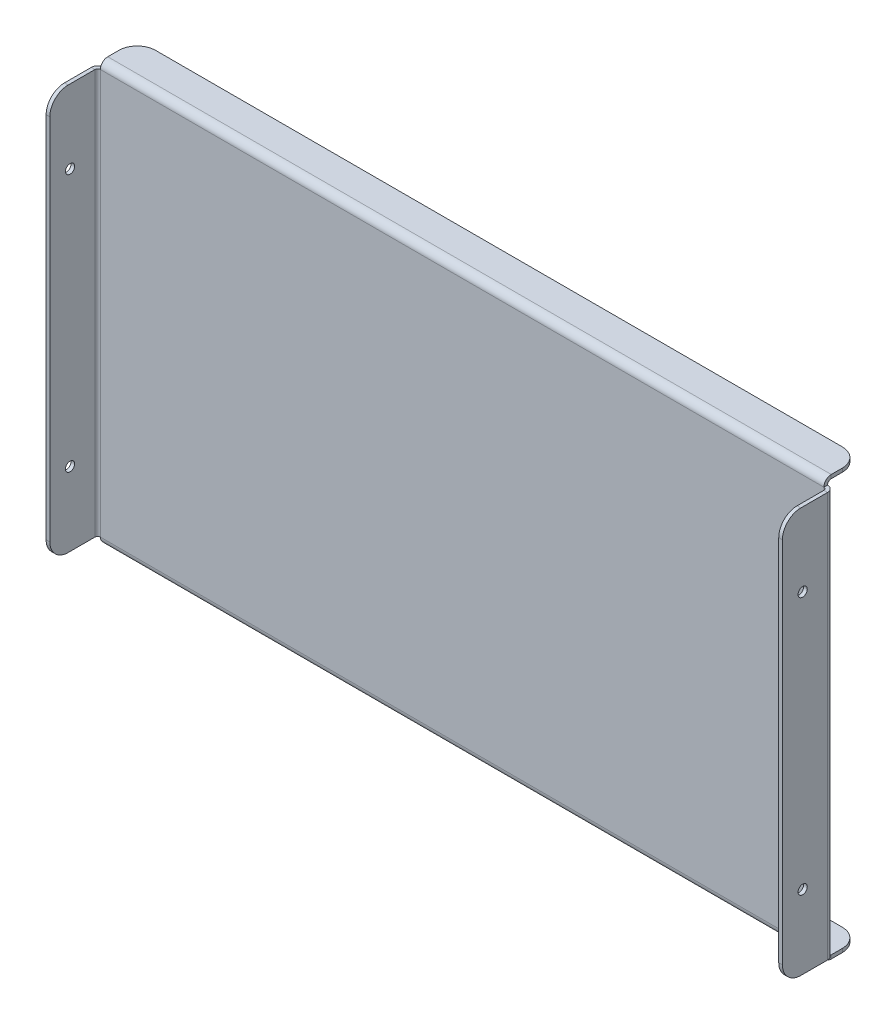
SolidWorks part; units mm, degrees
note: The reader was unsure of these and kept them because the rebuilt part matched: flange length of "Edge-Flange1", "Edge-Flange2", "Edge-Flange3".
material "ASTM A36 Steel"
ref_plane "Front Plane" through (0, 0, 0) normal (0, 0, 1) x (1, 0, 0)
ref_plane "Top Plane" through (0, 0, 0) normal (0, 1, 0) x (1, 0, 0)
ref_plane "Right Plane" through (0, 0, 0) normal (1, 0, 0) x (0, 0, -1)
sketch "Sketch1" plane through (0, 0, 0) normal (0, 0, 1) x (1, 0, 0)
  line L1 (-100, -55) -> (100, -55)
  line L2 (-100, -55) -> (-100, 55)
  line L3 (-100, 55) -> (100, 55)
  line L4 (100, -55) -> (100, 55)
  line L5 (-100, -55) -> (100, 55) construction
  line L6 (-100, 55) -> (100, -55) construction
  point P0 (0, 0)
  dimension "D1" = 110
  dimension "D2" = 200
base flange "Base-Flange1" sketch "Sketch1" thickness 1 reverse thickness direction no parameters "D1"=0.7366
edge flange "Edge-Flange1" sketch "Sketch8" flange angle 90 flange length 14 flange position material inside bend radius 0.7366 thickness 1 relief rectangular parameters "D6"=10
sketch "Sketch8" plane through (-100, 0, 0) normal (-1, 0, 0) x (0, -1, 0)
  line L0 (-55, 0) -> (55, 0) construction
  line L1 (-55, 0) -> (55, 0)
  line L2 (-55, 0) -> (-55, 13)
  line L3 (-55, 13) -> (55, 13)
  line L4 (55, 13) -> (55, 0)
bend "EdgeBend1" bend radius 0.7366 bend angle 90 parameters "D5"=1
edge flange "Edge-Flange2" sketch "Sketch13" flange angle 90 flange length 14 flange position material inside bend radius 0.7366 thickness 1 relief rectangular parameters "D6"=10
sketch "Sketch13" plane through (100, 0, 0) normal (1, 0, 0) x (0, 1, 0)
  line L0 (-55, 0) -> (55, 0) construction
  line L1 (-55, 0) -> (55, 0)
  line L2 (-55, 0) -> (-55, 13)
  line L3 (-55, 13) -> (55, 13)
  line L4 (55, 13) -> (55, 0)
bend "EdgeBend2" bend radius 0.7366 bend angle 90 parameters "D5"=2
sketch "Sketch14" plane through (-99, 0, 0) normal (1, 0, 0) x (0, 0, -1)
  line L0 (0, -55) -> (0, 55) construction
  line L1 (-0.7366, 55) -> (-0.7366, -55) construction
  circle A0 centre (-7.5, -35) radius 1.25
  circle A1 centre (-7.5, 35) radius 1.25
  point P8 (-0.7366, 0)
  dimension "D1" = 2.5
  dimension "D2" = 7.5
  dimension "D3" = 70
  dimension "D4" = 35
extrude "Cut-Extrude1" cut sketch "Sketch14" against normal blind 10 and the other way through all normal cut yes
edge flange "Edge-Flange3" sketch "Sketch17" flange profiles "Sketch17", "Sketch19" flange angle 90 flange length 10 flange position bend outside bend radius 1 thickness 1 relief rectangular parameters "D6"=10, "D8"=1
sketch "Sketch17" plane through (0, -55, -1) normal (0, -1, 0) x (-1, 0, 0)
  line L0 (98.2634, 0) -> (-98.2634, 0) construction
  line L1 (98.2634, 0) -> (-98.2634, 0)
  line L2 (-98.2634, 0) -> (-98.2634, 9)
  line L3 (-98.2634, 9) -> (98.2634, 9)
  line L4 (98.2634, 9) -> (98.2634, 0)
sketch "Sketch19" plane through (0, 55, -1) normal (0, 1, 0) x (1, 0, 0)
  line L0 (98.2634, 0) -> (-98.2634, 0) construction
  line L1 (98.2634, 0) -> (-98.2634, 0)
  line L2 (-98.2634, 0) -> (-98.2634, 9)
  line L3 (-98.2634, 9) -> (98.2634, 9)
  line L4 (98.2634, 9) -> (98.2634, 0)
bend "EdgeBend3" bend radius 1 bend angle 90 parameters "D5"=3
bend "EdgeBend4" bend radius 1 bend angle 90 parameters "D5"=5
fillet "Fillet1" radius 5 8 edges at (98.2634, -56.5, -10) (99.5, -55, 13) (99.5, 55, 13) (98.2634, 56.5, -10) (-98.2634, 56.5, -10) (-99.5, 55, 13) (-98.2634, -56.5, -10) (-99.5, -55, 13)
sketch "Bend-Lines1" [suppressed] plane through (0, 0, 0) normal (0, 1, 0) x (1, 0, 0)
sketch "Bounding-Box1" [suppressed] plane through (0, 0, 0) normal (0, 1, 0) x (1, 0, 0)
sheet metal parameters "Sheet-Metal1" thickness 1 parameters "D1"=0.7366
flat pattern "Flat-Pattern1" [suppressed]
sketch "Bend-Lines2" plane through (0, 0, 0) normal (0, 1, 0) x (1, 0, 0)
sketch3d "Bounding-Box2" [suppressed]
  line L0 (100, -55, 0) -> (-100, -55, 0) construction
  line L1 (100, 55, 0) -> (-100, 55, 0) construction
  line L2 (100, -55, 0) -> (100, 55, 0) construction
  line L3 (-100, -55, 0) -> (-100, 55, 0) construction
sheet metal parameters "Sheet-Metal2" thickness 1 parameters "D1"=0.7366
flat pattern "Flat-Pattern1"
sketch "Bend-Lines2" plane through (0, 0, 0) normal (0, 0, 1) x (1, 0, 0)
  line L0 (-99.2346, 55) -> (-99.2346, -55) construction
  line L1 (-99.2346, 55) -> (-99.2346, -55) construction
sketch3d "Bounding-Box2" [suppressed]
  line L0 (-112.4692, -55, 0) -> (100, -55, 0) construction
  line L1 (-112.4692, 55, 0) -> (100, 55, 0) construction
  line L2 (-112.4692, -55, 0) -> (-112.4692, 55, 0) construction
  line L3 (100, -55, 0) -> (100, 55, 0) construction
bend of the flat pattern "Flatten-<EdgeBend1>1"
sheet metal parameters "Sheet-Metal3" thickness 1 parameters "D1"=0.7366
flat pattern "Flat-Pattern1"
sketch "Bend-Lines2" plane through (0, 0, 0) normal (0, 0, 1) x (1, 0, 0)
  line L0 (-99.2346, 55) -> (-99.2346, -55) construction
  line L1 (-99.2346, 55) -> (-99.2346, -55) construction
  line L2 (99.2346, -55) -> (99.2346, 55) construction
  line L3 (99.2346, -55) -> (99.2346, 55) construction
sketch3d "Bounding-Box2" [suppressed]
  line L0 (-112.4692, -55, 0) -> (112.4692, -55, 0) construction
  line L1 (-112.4692, 55, 0) -> (112.4692, 55, 0) construction
  line L2 (-112.4692, -55, 0) -> (-112.4692, 55, 0) construction
  line L3 (112.4692, -55, 0) -> (112.4692, 55, 0) construction
bend of the flat pattern "Flatten-<EdgeBend1>1"
bend of the flat pattern "Flatten-<EdgeBend2>1"
sheet metal parameters "Sheet-Metal4" thickness 1 parameters "D1"=0.7366
flat pattern "Flat-Pattern1"
sketch "Bend-Lines2" plane through (0, 0, 0) normal (0, 0, 1) x (1, 0, 0)
  line L0 (-99.2346, 55) -> (-99.2346, -55) construction
  line L1 (-99.2346, 55) -> (-99.2346, -55) construction
  line L2 (99.2346, -55) -> (99.2346, 55) construction
  line L3 (99.2346, -55) -> (99.2346, 55) construction
sketch3d "Bounding-Box2" [suppressed]
  line L0 (-112.4692, -55, 0) -> (112.4692, -55, 0) construction
  line L1 (-112.4692, 55, 0) -> (112.4692, 55, 0) construction
  line L2 (-112.4692, -55, 0) -> (-112.4692, 55, 0) construction
  line L3 (112.4692, -55, 0) -> (112.4692, 55, 0) construction
bend of the flat pattern "Flatten-<EdgeBend1>1"
bend of the flat pattern "Flatten-<EdgeBend2>1"
sheet metal parameters "Sheet-Metal5" thickness 1 parameters "D1"=0.7366
flat pattern "Flat-Pattern1"
sketch "Bend-Lines2" plane through (0, 0, 0) normal (0, 0, 1) x (1, 0, 0)
  line L0 (-99.2346, 55) -> (-99.2346, -55) construction
  line L1 (-99.2346, 55) -> (-99.2346, -55) construction
  line L2 (99.2346, -55) -> (99.2346, 55) construction
  line L3 (99.2346, -55) -> (99.2346, 55) construction
  line L4 (-98.2634, -56.1781) -> (98.2634, -56.1781) construction
  line L5 (-98.2634, -56.1781) -> (98.2634, -56.1781) construction
  line L6 (98.2634, 56.1781) -> (-98.2634, 56.1781) construction
  line L7 (98.2634, 56.1781) -> (-98.2634, 56.1781) construction
sketch3d "Bounding-Box2" [suppressed]
  line L0 (-112.4692, 65.3562, 0) -> (112.4692, 65.3562, 0) construction
  line L1 (-112.4692, -65.3562, 0) -> (112.4692, -65.3562, 0) construction
  line L2 (-112.4692, 65.3562, 0) -> (-112.4692, -65.3562, 0) construction
  line L3 (112.4692, 65.3562, 0) -> (112.4692, -65.3562, 0) construction
bend of the flat pattern "Flatten-<EdgeBend1>1"
bend of the flat pattern "Flatten-<EdgeBend2>1"
bend of the flat pattern "Flatten-<EdgeBend3>1"
bend of the flat pattern "Flatten-<EdgeBend4>1"
